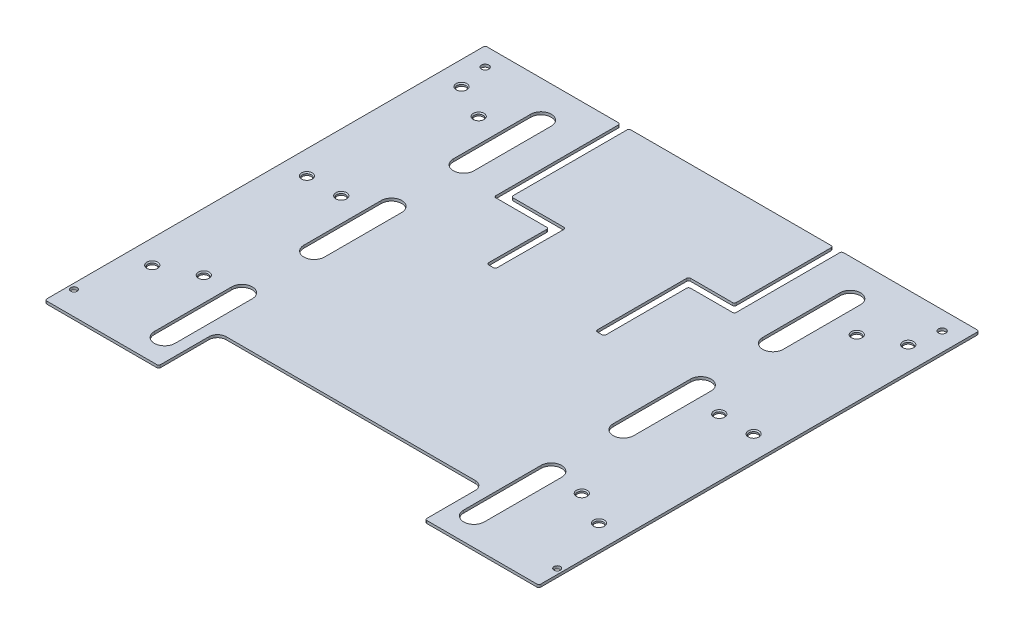
SolidWorks part; units mm, degrees
material "PC High Viscosity"
ref_plane "Front Plane" through (0, 0, 0) normal (0, 0, 1) x (1, 0, 0)
ref_plane "Top Plane" through (0, 0, 0) normal (0, 1, 0) x (1, 0, 0)
ref_plane "Right Plane" through (0, 0, 0) normal (1, 0, 0) x (0, 0, -1)
sketch "Sketch1" plane through (0, 0, 0) normal (0, 1, 0) x (1, 0, 0)
  line L1 (-146.05, 130.175) -> (146.05, 130.175)
  line L2 (-146.05, 130.175) -> (-146.05, -130.175)
  line L3 (-146.05, -130.175) -> (146.05, -130.175)
  line L4 (146.05, 130.175) -> (146.05, -130.175)
  line L5 (-146.05, 130.175) -> (146.05, -130.175) construction
  line L6 (-146.05, -130.175) -> (146.05, 130.175) construction
  line L16 (-135.128, 119.253) -> (135.128, 119.253) construction
  line L18 (-91.44, 18.923) -> (-91.44, -25.273) construction
  line L19 (91.44, 18.923) -> (91.44, -25.273) construction
  line L20 (-91.44, -3.175) -> (91.44, -3.175) construction
  line L21 (0, 127) -> (0, -88.9) construction
  circle A4 centre (-135.128, 119.253) radius 2.1527
  circle A6 centre (135.128, 119.253) radius 2.1527
  point P0 (0, 0)
  point P6 (0, 0)
  point P7 (0, 0)
  point P13 (0, -88.9)
  point P14 (0, -130.175)
  point P37 (0, 119.253)
  dimension "D9" = 4.3053
  dimension "D1" = 292.1
  dimension "D2" = 260.35
  dimension "D7" = 10.922
  dimension "D8" = 10.922
extrude "Boss-Extrude1" add sketch "Sketch1" along normal blind 1.5875 contours L1 L2 L3 L4 region at (0, 0, 0.0457)
sketch "Sketch5" plane through (0, 1.5875, 0) normal (0, 1, 0) x (1, 0, 0)
  line L0 (-91.44, 108.585) -> (-91.44, 62.865) construction
  line L1 (-85.344, 108.585) -> (-85.344, 62.865)
  line L2 (-97.536, 108.585) -> (-97.536, 62.865)
  line L3 (-146.05, 130.175) -> (-146.05, -130.175) construction
  line L4 (-146.05, 130.175) -> (146.05, 130.175) construction
  arc A0 (-85.344, 108.585) -> (-97.536, 108.585) centre (-91.44, 108.585) ccw
  arc A1 (-97.536, 62.865) -> (-85.344, 62.865) centre (-91.44, 62.865) ccw
  point P2 (-91.44, 85.725)
  dimension "D1" = 48.514
  dimension "D2" = 12.192
  dimension "D3" = 21.59
  dimension "D4" = 45.72
extrude "Cut-Extrude2" cut sketch "Sketch5" against normal through all
pattern_linear "LPattern2" count 3 spacing 88.392 along (0, 0, 1) of "Cut-Extrude2"
mirror "Mirror1" about plane through (0, 0, 0) normal (1, 0, 0) of "LPattern2", "Cut-Extrude2"
sketch "Sketch6" plane through (0, 1.5875, 0) normal (0, 1, 0) x (1, 0, 0)
  line L0 (-146.05, 130.175) -> (-146.05, -130.175) construction
  line L1 (146.05, 130.175) -> (146.05, -130.175) construction
  line L2 (-146.05, -130.175) -> (146.05, -130.175) construction
  circle A0 centre (-142.875, -116.1542) radius 1.8987
  circle A1 centre (142.875, -116.1542) radius 1.8987
  dimension "D1" = 3.7973
  dimension "D2" = 3.7973
  dimension "D3" = 3.175
  dimension "D4" = 3.175
  dimension "D5" = 14.0208
  dimension "D6" = 14.0208
extrude "Cut-Extrude3" cut sketch "Sketch6" against normal through all
sketch "Sketch7" plane through (0, 1.5875, 0) normal (0, 1, 0) x (1, 0, 0)
  line L0 (-146.05, -130.175) -> (146.05, -130.175) construction
  line L1 (-78.74, -130.175) -> (78.74, -130.175)
  line L2 (-78.74, -130.175) -> (-78.74, -95.377)
  line L3 (-78.74, -95.377) -> (78.74, -95.377)
  line L4 (78.74, -130.175) -> (78.74, -95.377)
  line L5 (-146.05, 130.175) -> (-146.05, -130.175) construction
  line L6 (146.05, 130.175) -> (146.05, -130.175) construction
  dimension "D1" = 67.31
  dimension "D2" = 67.31
  dimension "D3" = 34.798
extrude "Cut-Extrude4" cut sketch "Sketch7" against normal through all
fillet "Fillet1" radius 5.08 2 edges at (78.74, 0.7937, 95.377) (-78.74, 0.7937, 95.377)
sketch "Sketch8" plane through (0, 1.5875, 0) normal (0, 1, 0) x (1, 0, 0)
  line L0 (-63.5702, 132.7061) -> (-63.5702, 57.9933)
  line L1 (-146.05, 130.175) -> (146.05, 130.175) construction
  line L2 (-65.1577, 57.9933) -> (-61.9827, 57.9933) construction
  line L3 (-63.5702, 57.9933) -> (-31.2748, 57.9933)
  line L4 (-31.2748, 57.9933) -> (-31.3977, 18.9565)
  line L6 (62.2076, 130.175) -> (62.2076, 69.2873)
  line L7 (62.2076, 69.2873) -> (35.144, 69.2873)
  line L8 (35.144, 69.2873) -> (35.144, 16.7563)
  point P9 (-31.3977, 18.9565)
  point P10 (35.144, 16.7563)
  point P12 (-63.4203, 57.9933)
  point P15 (0, 0)
  point P16 (-63.5702, 132.7061)
  point P17 (-63.4203, 57.9933)
  point P18 (-31.2748, 36.9499)
extrude "Cut-Extrude-Thin1" cut sketch "Sketch8" against normal through all thin thin type mid plane wall 5.08
fillet "Fillet2" radius 1.143 22 edges at (-146.05, 0.7937, -130.175) (-146.05, 0.7937, 130.175) (-78.74, 0.7937, 130.175) (78.74, 0.7937, 130.175) (146.05, 0.7937, 130.175) (146.05, 0.7937, -130.175) (64.7476, 0.7937, -130.175) (64.7476, 0.7937, -66.7473) (37.684, 0.7937, -66.7473) (37.684, 0.7937, -16.7563) (32.604, 0.7937, -16.7563) (32.604, 0.7937, -71.8273) (59.6676, 0.7937, -71.8273) (59.6676, 0.7937, -130.175) (-61.0302, 0.7937, -130.175) (-61.0302, 0.7937, -60.5333) (-28.7268, 0.7937, -60.5333) (-28.8577, 0.7937, -18.9485) (-33.9377, 0.7937, -18.9645) (-33.8228, 0.7937, -55.4533) (-66.1102, 0.7937, -55.4533) (-66.1102, 0.7937, -130.175)
hole_wizard "#10 Clearance Hole1" positions "Sketch9" profile "Sketch10" hole size "#10" standard "ANSI Inch" end condition through all
sketch "Sketch9" plane through (0, 1.5875, 0) normal (0, 1, 0) x (1, 0, 0)
  point P0 (-132.08, 102.235)
  point P3 (-132.08, 10.795)
  point P6 (-111.76, 10.795)
  point P9 (-111.76, 92.075)
  point P12 (-132.08, -80.645)
  point P15 (-111.76, -70.485)
  point P18 (111.76, -70.485)
  point P21 (132.08, -80.645)
  point P24 (132.08, 10.795)
  point P27 (111.76, 10.795)
  point P30 (111.76, 92.075)
  point P33 (132.08, 102.235)
sketch "Sketch10" plane through (-132.08, 1.5875, -102.235) normal (1, 0, 0) x (0, 0, 1)
  line L0 (0, 0) -> (0, 1.5875)
  line L1 (0, 1.5875) -> (2.5527, 1.5875)
  line L2 (2.5527, 1.5875) -> (2.5527, 0.635)
  line L3 (2.5527, 0.635) -> (3.1877, 0)
  line L5 (3.1877, 0) -> (0, 0)
  line L6 (-2.5527, 0.635) -> (-3.1877, 0) construction
  line L11 (0, -6.35) -> (0, 107.95) construction
  dimension "Thru Hole Dia." = 5.1054
  dimension "Thru Hole Depth" = 1.5875
  dimension "Near C'Sink Dia." = 6.3754
  dimension "Near C'Sink Angle" = 90
